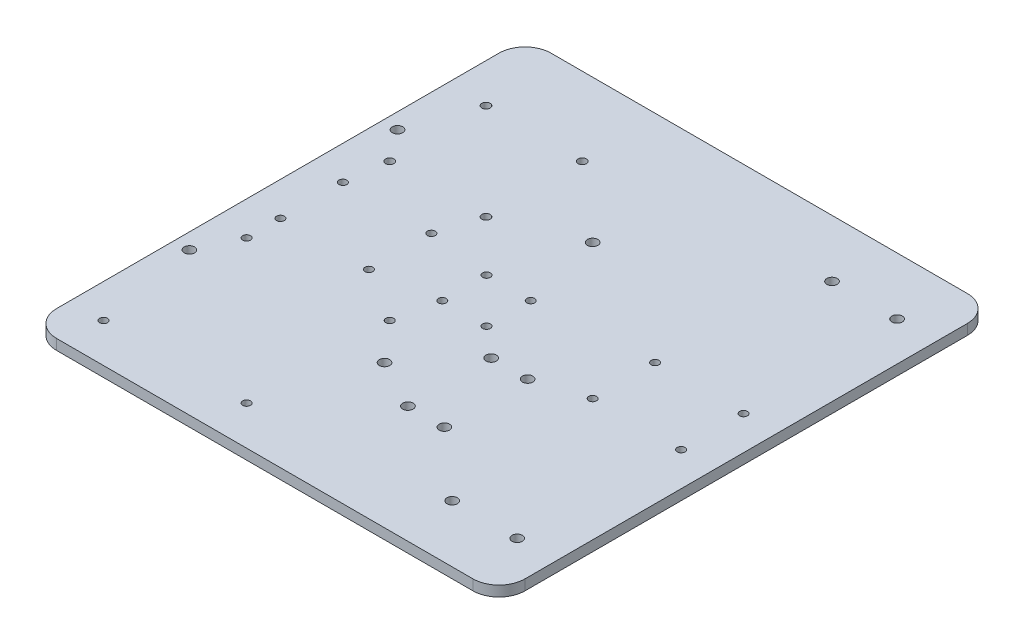
SolidWorks part; units mm, degrees
ref_plane "前视基准面" through (0, 0, 0) normal (0, 0, 1) x (1, 0, 0)
ref_plane "上视基准面" through (0, 0, 0) normal (0, 1, 0) x (1, 0, 0)
ref_plane "右视基准面" through (0, 0, 0) normal (1, 0, 0) x (0, 0, -1)
other "Configuration Table"
sketch "草图1" plane through (0, 0, 0) normal (0, 1, 0) x (1, 0, 0)
  line L1 (-90, -95) -> (90, -95)
  line L2 (-90, -95) -> (-90, 95)
  line L3 (-90, 95) -> (90, 95)
  line L4 (90, -95) -> (90, 95)
  line L5 (-90, -95) -> (90, 95) construction
  line L6 (-90, 95) -> (90, -95) construction
  point P0 (0, 0)
  dimension "D1" = 190
  dimension "D2" = 180
extrude "凸台-拉伸1" add sketch "草图1" along normal blind 4
sketch "草图2" plane through (0, 4, 0) normal (0, 1, 0) x (1, 0, 0)
  line L0 (90, -95) -> (90, 95) construction
  line L1 (66, -25) -> (85, -25) construction
  line L2 (66, -25) -> (66, 25) construction
  line L3 (66, 25) -> (85, 25) construction
  line L4 (85, -25) -> (85, 25) construction
  line L5 (66, -25) -> (85, 25) construction
  line L6 (66, 25) -> (85, -25) construction
  circle A0 centre (66, 25) radius 1.6
  circle A1 centre (66, -25) radius 1.6
  circle A2 centre (85, -25) radius 1.6
  circle A3 centre (85, 25) radius 1.6
  circle A7 centre (80.7, 7) radius 3
  point P0 (75.5, 0)
  dimension "D4" = 3.2
  dimension "D5" = 4.3
  dimension "D7" = 6
  dimension "D1" = 19
  dimension "D2" = 50
  dimension "D3" = 5
  dimension "D6" = 18
sketch "草图4" plane through (0, 4, 0) normal (0, 1, 0) x (1, 0, 0)
  line L0 (90, 95) -> (-90, 95) construction
  line L1 (-75, 65) -> (-38, 65) construction
  line L2 (-75, 65) -> (-75, 28) construction
  line L3 (-75, 28) -> (-38, 28) construction
  line L4 (-38, 65) -> (-38, 28) construction
  line L5 (-90, 95) -> (-90, -95) construction
  circle A0 centre (-75, 65) radius 1.6
  circle A1 centre (-38, 65) radius 1.6
  circle A2 centre (-38, 28) radius 1.6
  circle A3 centre (-75, 28) radius 1.6
  dimension "D4" = 3.2
  dimension "D1" = 37
  dimension "D2" = 30
  dimension "D3" = 15
extrude "切除-拉伸3" cut sketch "草图4" against normal blind 4
sketch "草图5" plane through (0, 4, 0) normal (0, 1, 0) x (1, 0, 0)
  line L5 (-90, 95) -> (-90, -95) construction
  line L7 (-22, -80) -> (-77, -80) construction
  line L8 (-22, -80) -> (-22, -25) construction
  line L9 (-22, -25) -> (-77, -25) construction
  line L10 (-77, -80) -> (-77, -25) construction
  line L11 (-90, -95) -> (90, -95) construction
  circle A8 centre (-77, -80) radius 1.5
  circle A9 centre (-77, -25) radius 1.5
  circle A10 centre (-22, -25) radius 1.5
  circle A11 centre (-22, -80) radius 1.5
  dimension "D2" = 3
  dimension "D1" = 55
  dimension "D3" = 13
  dimension "D4" = 15
extrude "切除-拉伸4" cut sketch "草图5" against normal blind 4
sketch "草图7" plane through (0, 0, 0) normal (0, -1, 0) x (1, 0, 0)
  line L0 (-90, 95) -> (90, 95) construction
  line L2 (90, 95) -> (90, -95) construction
  circle A0 centre (24, 50) radius 2
  circle A1 centre (10, 50) radius 2
  circle A2 centre (24, 18) radius 2
  circle A3 centre (10, 18) radius 2
  dimension "D2" = 4
  dimension "D5" = 4
  dimension "D1" = 80
  dimension "D3" = 45
  dimension "D6" = 14
  dimension "D7" = 32
extrude "切除-拉伸5" cut sketch "草图7" against normal blind 10
sketch "草图8" plane through (0, 0, 0) normal (0, -1, 0) x (1, 0, 0)
  line L1 (-18.5, -8.7) -> (-1.5, -8.7) construction
  line L2 (-18.5, -8.7) -> (-18.5, 8.3) construction
  line L3 (-18.5, 8.3) -> (-1.5, 8.3) construction
  line L4 (-1.5, -8.7) -> (-1.5, 8.3) construction
  line L5 (-18.5, -8.7) -> (-1.5, 8.3) construction
  line L6 (-18.5, 8.3) -> (-1.5, -8.7) construction
  circle A0 centre (-18.5, 8.3) radius 1.5
  circle A1 centre (-1.5, 8.3) radius 1.5
  circle A2 centre (-18.5, -8.7) radius 1.5
  circle A3 centre (-1.5, -8.7) radius 1.5
  point P0 (-10, -0.2)
  dimension "D4" = 3
  dimension "D1" = 17
  dimension "D2" = 0.2
  dimension "D3" = 10
extrude "切除-拉伸6" cut sketch "草图8" against normal blind 10
sketch "草图11" plane through (0, 0, 0) normal (0, -1, 0) x (1, 0, 0)
  line L0 (60, 95) -> (60, -95) construction
  line L1 (-90, 0) -> (90, 0) construction
  line L2 (90, 95) -> (90, -95) construction
  line L3 (-90, -95) -> (-90, 95) construction
  line L4 (90, -95) -> (-90, -95) construction
  line L5 (-90, 95) -> (90, 95) construction
  circle A0 centre (77, 12) radius 1.5
  circle A1 centre (43, 12) radius 1.5
  circle A2 centre (77, -12) radius 1.5
  circle A3 centre (43, -12) radius 1.5
  dimension "D1" = 3
  dimension "D2" = 24
  dimension "D3" = 34
  dimension "D4" = 30
extrude "切除-拉伸8" cut sketch "草图11" against normal blind 4
sketch "草图12" plane through (0, 0, 0) normal (0, -1, 0) x (1, 0, 0)
  line L0 (-90, -95) -> (-90, 95) construction
  line L1 (-9, -40) -> (-84, -40) construction
  line L2 (-9, -40) -> (-9, 40) construction
  line L3 (-9, 40) -> (-84, 40) construction
  line L4 (-84, -40) -> (-84, 40) construction
  line L5 (-9, -40) -> (-84, 40) construction
  line L6 (-9, 40) -> (-84, -40) construction
  circle A0 centre (-84, 40) radius 2
  circle A1 centre (-9, 40) radius 2
  circle A2 centre (-9, -40) radius 2
  circle A3 centre (-84, -40) radius 2
  point P0 (-46.5, 0)
  dimension "D4" = 4
  dimension "D1" = 6
  dimension "D2" = 75
  dimension "D3" = 80
extrude "切除-拉伸9" cut sketch "草图12" against normal blind 4
sketch "草图15" plane through (0, 4, 0) normal (0, 1, 0) x (1, 0, 0)
  line L1 (90, -95) -> (90, 95) construction
  line L2 (0, 0) -> (50000, 0) construction
  circle A0 centre (75, -73) radius 2
  circle A1 centre (50, -73) radius 2
  dimension "D2" = 4
  dimension "D5" = 4
  dimension "D1" = 73
  dimension "D3" = 15
  dimension "D4" = 25
extrude "切除-拉伸10" cut sketch "草图15" against normal through all
mirror "镜向2" about plane through (0, 0, 0) normal (0, 0, 1) of "切除-拉伸10"
fillet "圆角2" radius 10 4 edges at (-90, 2, 95) (90, 2, 95) (90, 2, -95) (-90, 2, -95)
mirror "镜向3" about plane through (0, 0, 0) normal (1, 0, 0) of "切除-拉伸8"
